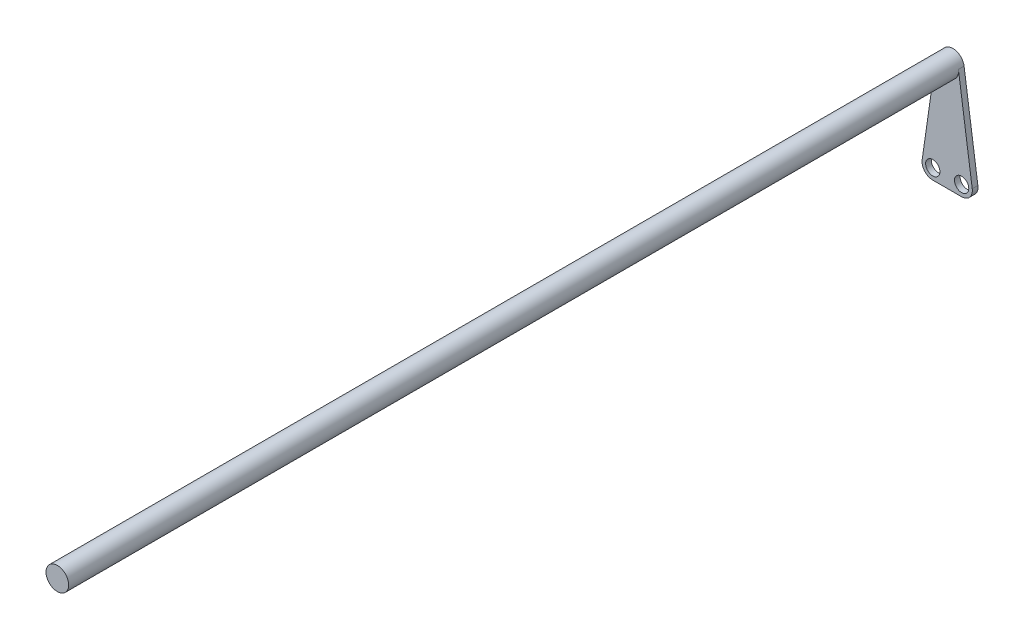
SolidWorks part; units mm, degrees
ref_plane "Front Plane" through (0, 0, 0) normal (0, 0, 1) x (1, 0, 0)
ref_plane "Top Plane" through (0, 0, 0) normal (0, 1, 0) x (1, 0, 0)
ref_plane "Right Plane" through (0, 0, 0) normal (1, 0, 0) x (0, 0, -1)
sketch "Sketch1" plane through (0, 0, 0) normal (0, 0, 1) x (1, 0, 0)
  circle A0 centre (0, 0) radius 6.35
  dimension "D1" = 12.7
extrude "Boss-Extrude1" add sketch "Sketch1" along normal mid plane 500
sketch "Sketch2" plane through (0, 0, -250) normal (0, 0, -1) x (-1, 0, 0)
  line L0 (-6.286, 0.8995) -> (-14.0199, -53.1501)
  line L3 (-8.0804, -60) -> (8.0804, -60)
  line L4 (14.0199, -53.1501) -> (6.286, 0.8995)
  circle A3 centre (0, 0) radius 6.35 construction
  arc A4 (6.286, 0.8995) -> (-6.286, 0.8995) centre (0, 0) ccw
  arc A5 (8.0804, -60) -> (14.0199, -53.1501) centre (8.0804, -54) ccw
  arc A6 (-14.0199, -53.1501) -> (-8.0804, -60) centre (-8.0804, -54) ccw
  point P9 (0, -60)
  point P13 (15, -60)
  point P16 (-15, -60)
  dimension "D1" = 60
  dimension "D3" = 6
  dimension "D2" = 30
extrude "Boss-Extrude2" add sketch "Sketch2" along normal mid plane 3.175
sketch "Sketch3" plane through (0, 0, -248.4125) normal (0, 0, 1) x (1, 0, 0)
  circle A2 centre (-8.0804, -54) radius 4
  circle A3 centre (8.0804, -54) radius 4
  arc A4 (-14.0199, -53.1501) -> (-8.0804, -60) centre (-8.0804, -54) ccw construction
  arc A5 (8.0804, -60) -> (14.0199, -53.1501) centre (8.0804, -54) ccw construction
  dimension "D1" = 8
  dimension "D2" = 8
extrude "Cut-Extrude1" cut sketch "Sketch3" against normal up to next
